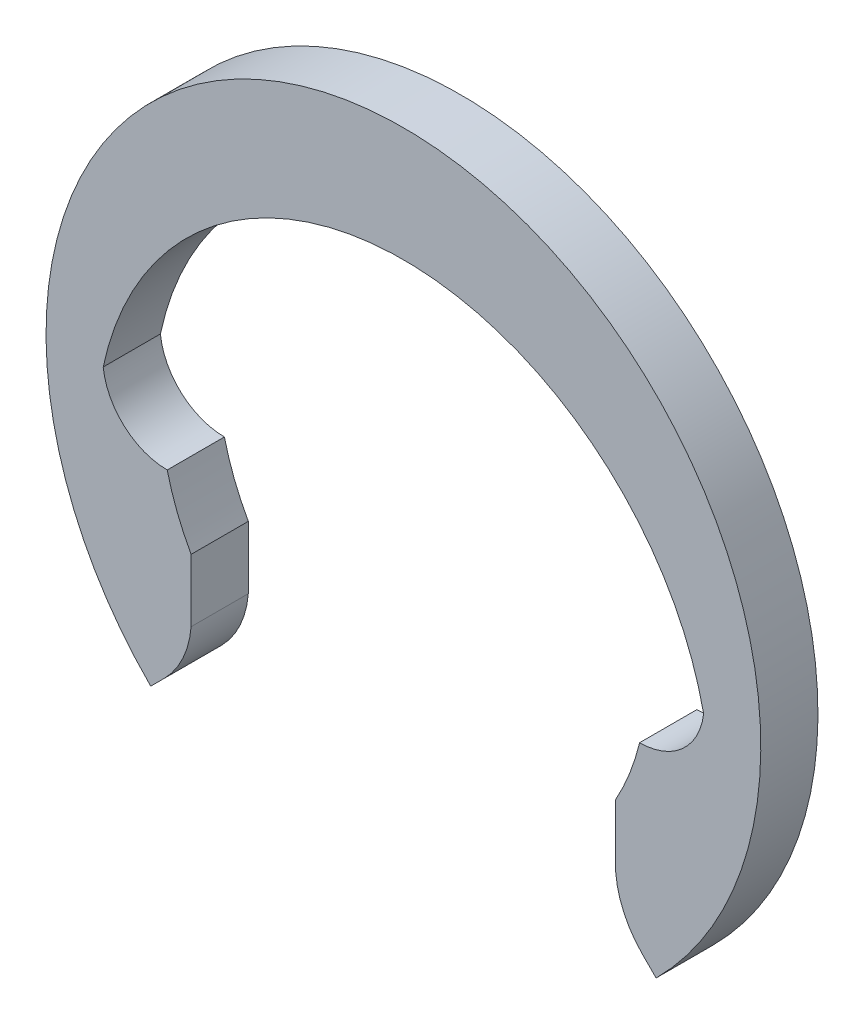
SolidWorks part; units mm, degrees
ref_plane "Front" through (0, 0, 0) normal (0, 0, 1) x (1, 0, 0)
ref_plane "Top" through (0, 0, 0) normal (0, 1, 0) x (1, 0, 0)
ref_plane "Right" through (0, 0, 0) normal (1, 0, 0) x (0, 0, -1)
sketch "Layout" plane through (0, 0, 0) normal (0, 0, 1) x (1, 0, 0)
  line L0 (0, 5) -> (0, -5) construction
  line L1 (-3.4, 0) -> (-5, 0) construction
  line L2 (-5, 0) -> (-5.8, 0) construction
  line L3 (-3.4, 0) -> (3.4, 0) construction
  line L4 (-2.9698, -2.9698) -> (-2.9698, -1.6553) construction
  line L5 (-3.3045, -0.8) -> (3.3045, -0.8) construction
  line L6 (-3.4, 0) -> (-3.4, -0.8) construction
  line L7 (0, 0) -> (-2.4042, -2.4042) construction
  line L8 (-2.4042, -2.4042) -> (-3.5355, -3.5355) construction
  circle A0 centre (0, 0) radius 5 construction
  circle A1 centre (0, 0) radius 3.4 construction
  arc A2 (0, 3.4) -> (-4.2, 0) centre (0, -0.8941) ccw construction
  circle A3 centre (0, 0) radius 5.1 construction
  arc A4 (-4.2, 0) -> (-3.3045, -0.8) centre (-3.3045, 0.1012) ccw construction
  dimension "D1" = 45
sketch "Sketch2" plane through (0, 0, 0) normal (0, 0, 1) x (1, 0, 0)
  line L0 (-2.9698, -2.9698) -> (-2.9698, -2.5317) construction
  line L1 (-2.9698, -2.5317) -> (-2.9698, -2.0935)
  line L2 (-2.9698, -2.0935) -> (-2.9698, -1.6553)
  line L4 (0, 5) -> (0, -5) construction
  line L5 (-2.9698, -2.9698) -> (-3.1584, -3.1584) construction
  line L6 (0, 5) -> (0, 3.4) construction
  line L7 (-3.1584, -3.1584) -> (-3.347, -3.347) construction
  line L8 (-3.347, -3.347) -> (-3.5355, -3.5355)
  line L9 (-2.4042, -2.4042) -> (-3.5355, -3.5355) construction
  line L10 (2.9698, -2.0935) -> (2.9698, -1.6553)
  line L11 (2.9698, -2.5317) -> (2.9698, -2.0935)
  line L12 (3.347, -3.347) -> (3.5355, -3.5355)
  circle A0 centre (0, 0) radius 5 construction
  arc A1 (0, 3.4) -> (-4.2, 0) centre (0, -0.8941) ccw construction
  arc A2 (-4.2, 0) -> (-3.3045, -0.8) centre (-3.3045, 0.1012) ccw construction
  circle A3 centre (0, 0) radius 3.4 construction
  arc A4 (3.5355, -3.5355) -> (-3.5355, -3.5355) centre (0, 0) ccw
  arc A5 (4.2, 0) -> (-4.2, 0) centre (0, -0.8941) ccw
  arc A6 (-4.2, 0) -> (-3.3045, -0.8) centre (-3.3045, 0.1012) ccw
  arc A7 (-3.3045, -0.8) -> (-2.9698, -1.6553) centre (0, 0) ccw
  arc A8 (-2.9698, -2.5317) -> (-3.347, -3.347) centre (-4.2678, -2.4262) cw
  arc A9 (2.9698, -2.5317) -> (3.347, -3.347) centre (4.2678, -2.4262) ccw
  arc A10 (3.3045, -0.8) -> (2.9698, -1.6553) centre (0, 0) cw
  arc A11 (4.2, 0) -> (3.3045, -0.8) centre (3.3045, 0.1012) cw
extrude "Boss-Extrude1" add sketch "Sketch2" along normal blind 0.8
ref_axis "Center Axis 1" through (0, 0, 0.8) along (0, 0, -1)
ref_plane "Contact Plane 1" through (0, 0, 0.8) normal (0, 0, 1) x (1, 0, 0)
ref_plane "Contact Plane 2" through (0, 0, 0) normal (0, 0, -1) x (-1, 0, 0)
equation "\"D1@Boss-Extrude1\"=\"thickness@Layout\""
